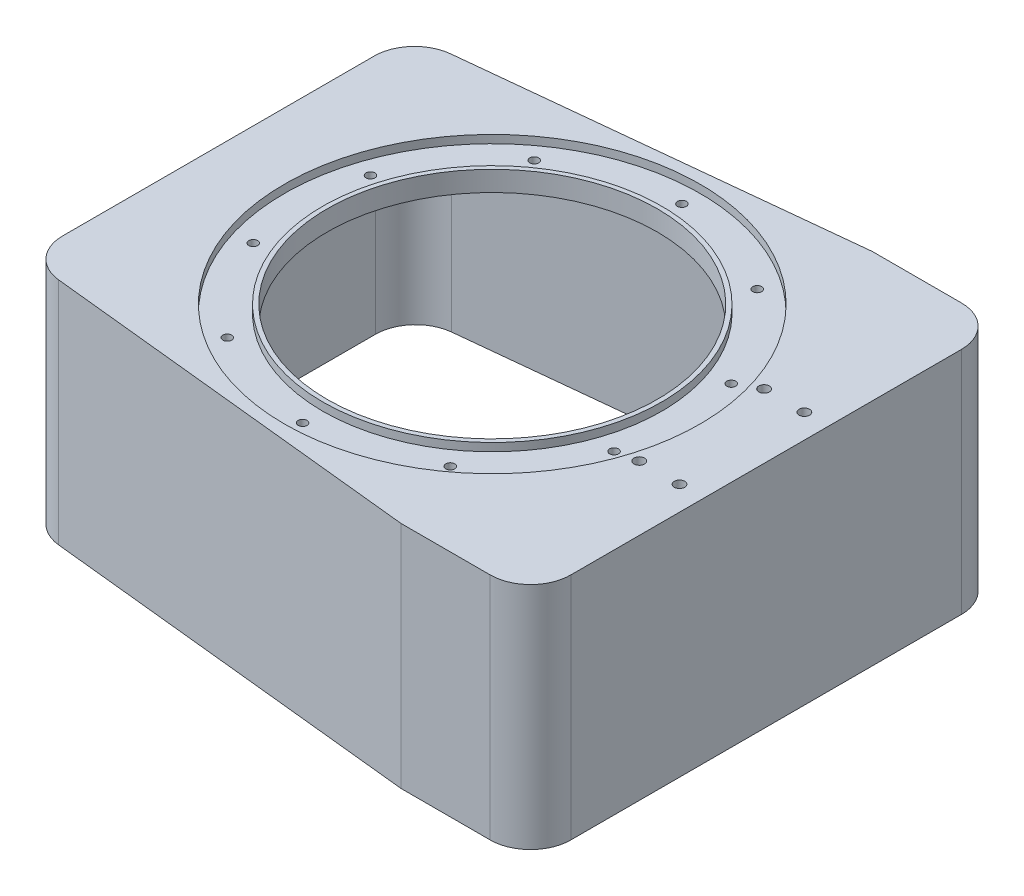
SolidWorks part; units mm, degrees
ref_plane "정면" through (0, 0, 0) normal (0, 0, 1) x (1, 0, 0)
ref_plane "윗면" through (0, 0, 0) normal (0, 1, 0) x (1, 0, 0)
ref_plane "우측면" through (0, 0, 0) normal (1, 0, 0) x (0, 0, -1)
sketch "스케치1" plane through (0, 0, 0) normal (0, 1, 0) x (1, 0, 0)
  line L0 (-65, -45) -> (36, -55.5)
  line L1 (-65, 45) -> (65, 45) construction
  line L2 (-65, 45) -> (-65, -45)
  line L3 (-65, -45) -> (65, -45) construction
  line L4 (65, 45) -> (65, -45) construction
  line L5 (-65, 45) -> (65, -45) construction
  line L6 (-65, -45) -> (65, 45) construction
  line L7 (65, 55.5) -> (36, 55.5)
  line L8 (65, 55.5) -> (65, -55.5)
  line L9 (65, -55.5) -> (36, -55.5)
  line L10 (36, 55.5) -> (36, -55.5) construction
  line L11 (65, 55.5) -> (36, -55.5) construction
  line L12 (65, -55.5) -> (36, 55.5) construction
  line L13 (-65, 45) -> (36, 55.5)
  line L20 (-68, -47.7043) -> (35.8445, -58.5)
  line L21 (68, -58.5) -> (35.8445, -58.5)
  line L22 (68, 58.5) -> (68, -58.5)
  line L23 (68, 58.5) -> (35.8445, 58.5)
  line L24 (-68, 47.7043) -> (35.8445, 58.5)
  line L25 (-68, 47.7043) -> (-68, -47.7043)
  point P0 (0, 0)
  point P9 (50.5, 0)
  point P10 (0, 0)
  point P11 (0, 0)
  dimension "D1" = 90
  dimension "D2" = 130
  dimension "D3" = 10.5
  dimension "D4" = 10.5
  dimension "D5" = 29
  dimension "D6" = 3
extrude "보스-돌출1" add sketch "스케치1" along normal blind 55
sketch "스케치2" plane through (0, 55, 0) normal (0, 1, 0) x (1, 0, 0)
  line L4 (-68, 47.7043) -> (35.8445, 58.5)
  line L10 (35.8445, 58.5) -> (68, 58.5)
  line L11 (68, 58.5) -> (68, -58.5)
  line L12 (68, -58.5) -> (35.8445, -58.5)
  line L14 (35.8445, -58.5) -> (-68, -47.7043)
  line L15 (-68, -47.7043) -> (-68, 47.7043)
extrude "보스-돌출2" add sketch "스케치2" along normal blind 2
sketch "스케치3" plane through (0, 55, 0) normal (0, -1, 0) x (1, 0, 0)
  circle A2 centre (0, 0) radius 53
  dimension "D1" = 106
extrude "보스-돌출3" add sketch "스케치3" along normal blind 3
sketch "스케치4" plane through (0, 57, 0) normal (0, 1, 0) x (1, 0, 0)
  circle A0 centre (0, 0) radius 51.6
  dimension "D1" = 103.2
extrude "컷-돌출1" cut sketch "스케치4" against normal blind 2
sketch "스케치5" plane through (0, 55, 0) normal (0, 1, 0) x (1, 0, 0)
  circle A0 centre (0, 0) radius 41
  dimension "D1" = 82
extrude "컷-돌출2" cut sketch "스케치5" against normal through all
sketch "스케치6" plane through (0, 55, 0) normal (0, 1, 0) x (1, 0, 0)
  circle A0 centre (0, 0) radius 42.1
  circle A1 centre (0, 0) radius 41
  circle A2 centre (0, 0) radius 41 construction
  dimension "D1" = 84.2
extrude "보스-돌출4" add sketch "스케치6" along normal blind 2
sketch "스케치9" plane through (0, 55, 0) normal (0, -1, 0) x (1, 0, 0)
  line L0 (65, 55.5) -> (65, -55.5) construction
  line L1 (41, -23.5) -> (65, -23.5)
  line L2 (41, -23.5) -> (41, 23.5)
  line L3 (41, 23.5) -> (65, 23.5)
  line L4 (65, -23.5) -> (65, 23.5)
  line L5 (41, -23.5) -> (65, 23.5) construction
  line L6 (41, 23.5) -> (65, -23.5) construction
  arc A0 (7.2113, -52.5071) -> (7.2113, 52.5071) centre (0, 0) ccw construction
  point P0 (53, 0)
  dimension "D1" = 47
extrude "보스-돌출6" add sketch "스케치9" along normal blind 9
sketch "스케치10" plane through (0, 46, 0) normal (0, -1, 0) x (1, 0, 0)
  line L0 (65, 55.5) -> (65, -55.5) construction
  line L1 (41, -18.5) -> (65, -18.5)
  line L2 (41, -18.5) -> (41, 18.5)
  line L3 (41, 18.5) -> (65, 18.5)
  line L4 (65, -18.5) -> (65, 18.5)
  line L5 (41, -18.5) -> (65, 18.5) construction
  line L6 (41, 18.5) -> (65, -18.5) construction
  line L7 (41, 0) -> (41, 23.5) construction
  line L8 (41, -23.5) -> (65, -23.5) construction
  point P0 (53, 0)
  dimension "D1" = 37
  dimension "D2" = 5
extrude "컷-돌출6" cut sketch "스케치10" against normal blind 6
sketch "스케치7" plane through (0, 55, 0) normal (0, 1, 0) x (1, 0, 0)
  circle A0 centre (0, 0) radius 47.1 construction
  circle A1 centre (0, 0) radius 51.6 construction
  circle A2 centre (0, 47.1) radius 1.1
  circle A3 centre (27.6847, 38.1047) radius 1.1
  circle A4 centre (44.7948, 14.5547) radius 1.1
  circle A5 centre (44.7948, -14.5547) radius 1.1
  circle A6 centre (27.6847, -38.1047) radius 1.1
  circle A7 centre (0, -47.1) radius 1.1
  circle A8 centre (-27.6847, -38.1047) radius 1.1
  circle A9 centre (-44.7948, -14.5547) radius 1.1
  circle A10 centre (-44.7948, 14.5547) radius 1.1
  circle A11 centre (-27.6847, 38.1047) radius 1.1
  point P27 (0, 0)
  dimension "D1" = 4.5
  dimension "D2" = 2.2
  dimension "D3" = 10
extrude "컷-돌출3" cut sketch "스케치7" against normal through all
fillet "필렛1" radius 10 8 edges at (-65, 27.5, -45) (-65, 27.5, 45) (65, 27.5, 55.5) (65, 27.5, -55.5) (68, 28.5, -58.5) (68, 28.5, 58.5) (-68, 28.5, 47.7043) (-68, 28.5, -47.7043)
sketch "스케치11" plane through (0, 52, 0) normal (0, -1, 0) x (1, 0, 0)
  line L0 (65, -18.5) -> (65, 18.5) construction
  line L1 (52, 15.5) -> (62, 15.5) construction
  line L2 (52, 15.5) -> (52, -15.5) construction
  line L3 (52, -15.5) -> (62, -15.5) construction
  line L4 (62, 15.5) -> (62, -15.5) construction
  line L5 (65, 18.5) -> (41, 18.5) construction
  line L6 (41, -18.5) -> (65, -18.5) construction
  circle A1 centre (52, 15.5) radius 1.3
  circle A2 centre (52, -15.5) radius 1.3
  circle A3 centre (62, 15.5) radius 1.3
  circle A4 centre (62, -15.5) radius 1.3
  dimension "D5" = 2.6
  dimension "D1" = 3
  dimension "D2" = 3
  dimension "D3" = 3
  dimension "D4" = 10
  dimension "D6" = 31
extrude "컷-돌출7" cut sketch "스케치11" against normal up to next
fillet "필렛2" radius 4.5 4 edges at (53, 46, 23.5) (53, 46, -23.5) (56.2526, 55, -23.5) (56.2526, 55, 23.5)
